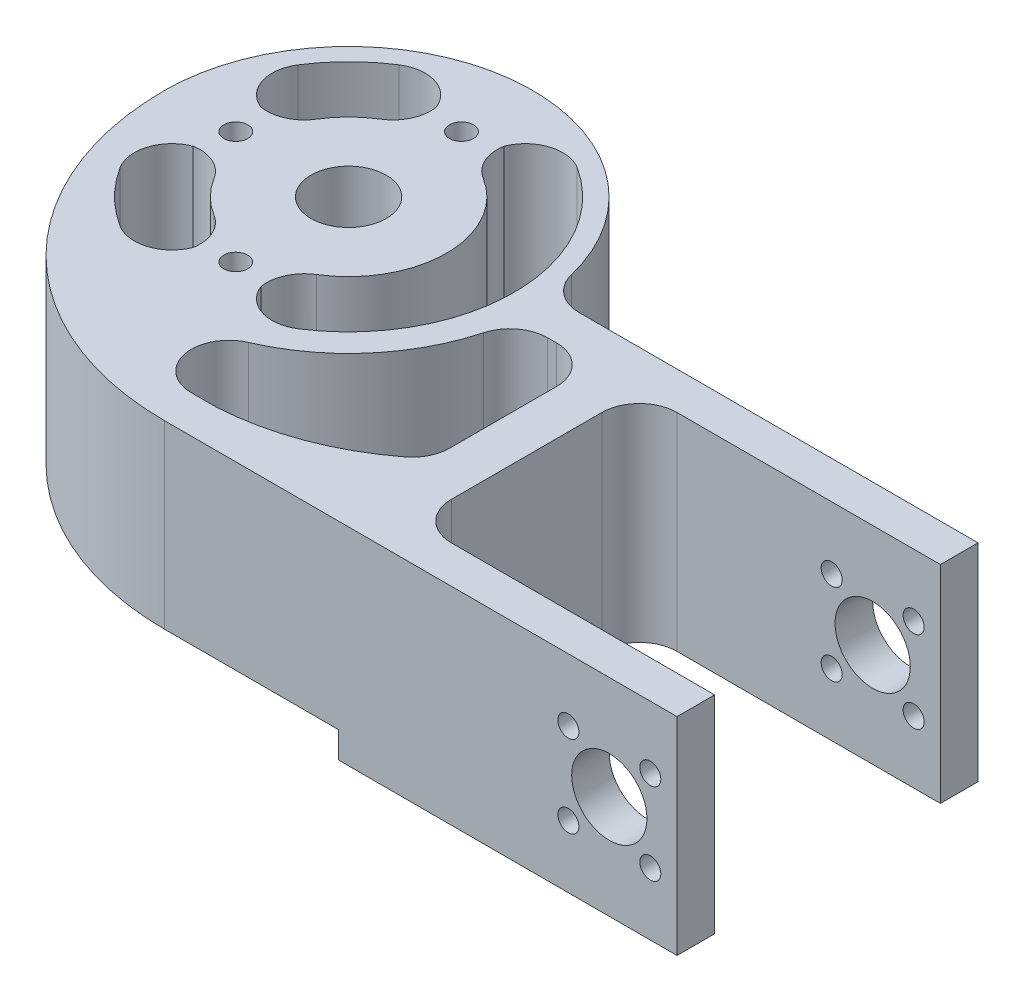
SolidWorks part; units mm, degrees
material "6061-T6 (SS)"
ref_plane "Front Plane" through (0, 0, 0) normal (0, 0, 1) x (1, 0, 0)
ref_plane "Top Plane" through (0, 0, 0) normal (0, 1, 0) x (1, 0, 0)
ref_plane "Right Plane" through (0, 0, 0) normal (1, 0, 0) x (0, 0, -1)
sketch "Sketch1" plane through (0, 0, 0) normal (0, 1, 0) x (1, 0, 0)
  circle A0 centre (0, 0) radius 31.0896
  dimension "D1" = 62.1792
extrude "Boss-Extrude1" add sketch "Sketch1" along normal blind 34.925
sketch "Sketch2" plane through (0, 34.925, 0) normal (0, 1, 0) x (1, 0, 0)
  line L0 (0, 0) -> (-31.0896, 0) construction
  line L1 (0, 0) -> (30.9857, 2.54) construction
  line L2 (46.5427, -48.26) -> (17.1704, -48.26)
  line L4 (46.5427, -48.26) -> (46.5427, 2.54)
  line L7 (30.9857, 2.54) -> (46.5427, 2.54)
  circle A0 centre (0, 0) radius 31.0896 construction
  arc A1 (17.1704, -48.26) -> (-31.0896, 0) centre (17.1704, 0) cw
  circle A2 centre (0, 0) radius 31.0896
  arc A3 (-31.0896, 0) -> (30.9857, 2.54) centre (0, 0) ccw
  dimension "D3" = 2.54
  dimension "D1" = 50.8
  dimension "D2" = 15.557
  dimension "D4" = 0
extrude "Boss-Extrude2" add sketch "Sketch2" against normal blind 30.48
sketch "Sketch3" plane through (0, 34.925, 0) normal (0, 1, 0) x (1, 0, 0)
  line L0 (46.5427, -0.3336) -> (46.5427, -48.26)
  line L1 (17.1704, -48.26) -> (46.5427, -48.26) construction
  line L2 (46.5427, -48.26) -> (103.6927, -48.26)
  line L3 (103.6927, -48.26) -> (103.6927, -41.91)
  line L4 (103.6927, -41.91) -> (52.8927, -41.91)
  line L5 (52.8927, -41.91) -> (52.8927, -3.81)
  line L6 (52.8927, -3.81) -> (103.6927, -3.81)
  line L7 (103.6927, -3.81) -> (103.6927, 2.54)
  line L8 (103.6927, 2.54) -> (46.5427, 2.54)
  line L9 (46.5427, -0.3336) -> (46.5427, 2.54)
  line L10 (46.5427, -48.26) -> (46.5427, 2.54) construction
  dimension "D1" = 57.15
  dimension "D2" = 38.1
  dimension "D3" = 6.35
  dimension "D4" = 6.35
extrude "Boss-Extrude3" add sketch "Sketch3" against normal up to surface (34.925 mm away) up to face at (0, 0, 31.0896)
sketch "Sketch4" plane through (0, 0, -2.54) normal (0, 0, -1) x (-1, 0, 0)
  line L0 (-103.6927, 17.4625) -> (-92.2627, 17.4625) construction
  line L1 (-103.6927, 0) -> (-103.6927, 34.925) construction
  line L2 (-92.2627, 17.4625) -> (-99.1775, 10.5477) construction
  line L3 (-92.2627, 17.4625) -> (-99.1775, 24.3773) construction
  line L4 (-92.2627, 17.4625) -> (-99.1775, 10.5477) construction
  line L5 (-92.2627, 17.4625) -> (-85.3479, 10.5477) construction
  line L6 (-92.2627, 17.4625) -> (-85.3479, 24.3773) construction
  line L8 (-99.1775, 24.3773) -> (-103.6927, 24.3773) construction
  line L9 (-103.6927, 0) -> (-103.6927, 34.925) construction
  line L10 (-99.1775, 10.5477) -> (-103.6927, 10.5477) construction
  circle A0 centre (-92.2627, 17.4625) radius 6.35
  circle A1 centre (-85.3479, 10.5477) radius 1.778
  circle A3 centre (-99.1775, 24.3773) radius 1.778
  circle A4 centre (-99.1775, 10.5477) radius 1.778
  circle A5 centre (-85.3479, 24.3773) radius 1.778
  dimension "D1" = 11.43
  dimension "D2" = 12.7
  dimension "D3" = 3.556
  dimension "D5" = 19.558
  dimension "D4" = 19.558
extrude "Cut-Extrude1" cut sketch "Sketch4" against normal up to surface (50.8 mm away) up to face at (53.3542, 12.7529, 48.26)
fillet "Fillet8" radius 6.35 1 edges at (30.9857, 19.685, -2.54)
fillet "Fillet9" radius 6.35 1 edges at (52.8927, 17.4625, 41.91)
fillet "Fillet10" radius 6.35 1 edges at (52.8927, 17.4625, 3.81)
sketch "Sketch11" plane through (0, 4.445, 0) normal (0, -1, 0) x (-1, 0, 0)
  line L0 (-46.5427, -48.26) -> (-46.5427, 2.54)
  line L1 (-103.6927, -3.81) -> (-32.1601, -3.81)
  line L2 (-103.6927, -41.91) -> (-14.7927, -41.91)
  line L3 (-18.1864, 0) -> (-32.385, 0) construction
  line L4 (-45.2727, -3.81) -> (-45.2727, -31.1827)
  circle A0 centre (0, 0) radius 32.385
  arc A2 (-17.1704, -48.26) -> (31.0896, 0) centre (-17.1704, 0) ccw construction
  circle A3 centre (-17.1704, 0) radius 41.9774
  dimension "D1" = 64.77
  dimension "D3" = 88.9
  dimension "D2" = 14.1986
  dimension "D4" = 1.27
sketch "Sketch12" plane through (0, 0, 0) normal (0, -1, 0) x (1, 0, 0)
  line L0 (0, 0) -> (0, -19.05) construction
  line L1 (0, 0) -> (0, 19.05) construction
  line L2 (0, 0) -> (-19.05, 0) construction
  line L3 (0, 0) -> (19.05, 0) construction
  circle A0 centre (0, 19.05) radius 2.0193
  circle A1 centre (-19.05, 0) radius 2.0193
  circle A2 centre (0, -19.05) radius 2.0193
  dimension "D1" = 4.0386
  dimension "D2" = 19.05
extrude "Cut-Extrude7" cut sketch "Sketch12" against normal up to surface (34.925 mm away) up to face at (56.2464, 34.925, 17.0919)
extrude "Cut-Extrude8" cut sketch "Sketch11" against normal through all contours L0 A3 L2 A0 L1 region at (27.27, 4.445, 26.5567)
fillet "Fillet11" radius 6.35 4 edges at (32.1601, 19.685, 3.81) (-12.1864, 19.685, 30.0047) (45.2727, 19.685, 31.1827) (45.2727, 19.685, 3.81)
sketch "Sketch14" plane through (0, 0, 0) normal (0, -1, 0) x (1, 0, 0)
  line L0 (0, 0) -> (-10.414, -10.414) construction
  line L1 (-10.414, -10.414) -> (10.414, -10.414)
  line L2 (-10.414, -10.414) -> (-10.414, 10.414)
  line L3 (-10.414, 10.414) -> (10.414, 10.414)
  line L4 (10.414, -10.414) -> (10.414, 10.414)
  line L5 (0, 0) -> (10.414, 10.414) construction
  line L6 (-10.414, 10.414) -> (0, 0) construction
  line L7 (0, 0) -> (10.414, -10.414) construction
  arc A0 (10.414, -10.414) -> (10.414, 10.414) centre (10.414, 0) ccw
  circle A1 centre (0, 0) radius 6.35
  dimension "D1" = 12.7
  dimension "D3" = 20.828
sketch "Sketch13" plane through (0, 0, 0) normal (0, -1, 0) x (1, 0, 0)
  line L0 (0, 0) -> (7.4507, 26.9283)
  line L1 (0, 0) -> (7.4507, -26.9283)
  line L2 (0, 0) -> (-7.4507, 26.9283)
  line L3 (0, 0) -> (-26.9283, 7.4507)
  line L4 (0, 0) -> (-26.9283, -7.4507)
  line L5 (0, 0) -> (-7.4507, -26.9283)
  line L6 (0, 0) -> (26.9283, 7.4507)
  line L7 (0, 0) -> (27.166, -6.531)
  circle A0 centre (0, 0) radius 27.94
  circle A1 centre (0, 0) radius 16.51
  circle A2 centre (0, 19.05) radius 2.0193 construction
  circle A3 centre (0, -19.05) radius 2.0193 construction
  circle A4 centre (-19.05, 0) radius 2.0193 construction
  circle A5 centre (-19.05, 0) radius 2.0193 construction
  dimension "D1" = 55.88
  dimension "D2" = 33.02
  dimension "D3" = 5.08
  dimension "D4" = 5.08
  dimension "D5" = 5.08
  dimension "D6" = 5.08
  dimension "D7" = 5.08
  dimension "D8" = 5.08
  dimension "D9" = 13.9817
extrude "Cut-Extrude9" cut sketch "Sketch13" against normal through all contours A1 L2 A0 L3 | A1 L4 A0 L5 | A1 L1 A0 L7 | A1 L6 A0 L0 | L7 A0 L6 region at (15.3599, 0, 15.3599) region at (15.5716, 0, -15.051) region at (-15.3599, 0, 15.3599) region at (-15.3599, 0, -15.3599) region at (22.4702, 0, 0.382)
fillet "Fillet14" radius 6.35 12 edges at (4.4027, 17.4625, 15.9122) (7.4507, 17.4625, 26.9283) (-26.9283, 17.4625, 7.4507) (-4.4027, 17.4625, 15.9122) (-15.9122, 17.4625, 4.4027) (-7.4507, 17.4625, 26.9283) (-7.4507, 17.4625, -26.9283) (-26.9283, 17.4625, -7.4507) (-4.4027, 17.4625, -15.9122) (-15.9122, 17.4625, -4.4027) (7.4507, 17.4625, -26.9283) (4.4027, 17.4625, -15.9122)
extrude "Cut-Extrude10" cut sketch "Sketch14" against normal blind 12.7 contours L1 L4 L3 L2 | L4 A0 region at (-10.1194, 0, 0) region at (14.8338, 0, 0)
fillet "Fillet17" radius 2.54 2 edges at (13.0872, 6.35, -10.0651) (13.0872, 6.35, 10.0651)
extrude "Cut-Extrude11" cut sketch "Sketch14<3>" against normal through all contours A1 region at (0, 0, 0)
sketch "Sketch14<3>" plane through (0, 0, 0) normal (0, -1, 0) x (1, 0, 0) same geometry as "Sketch14"
fillet "Fillet18" radius 3.556 2 edges at (-10.414, 6.35, 10.414) (-10.414, 6.35, -10.414)
